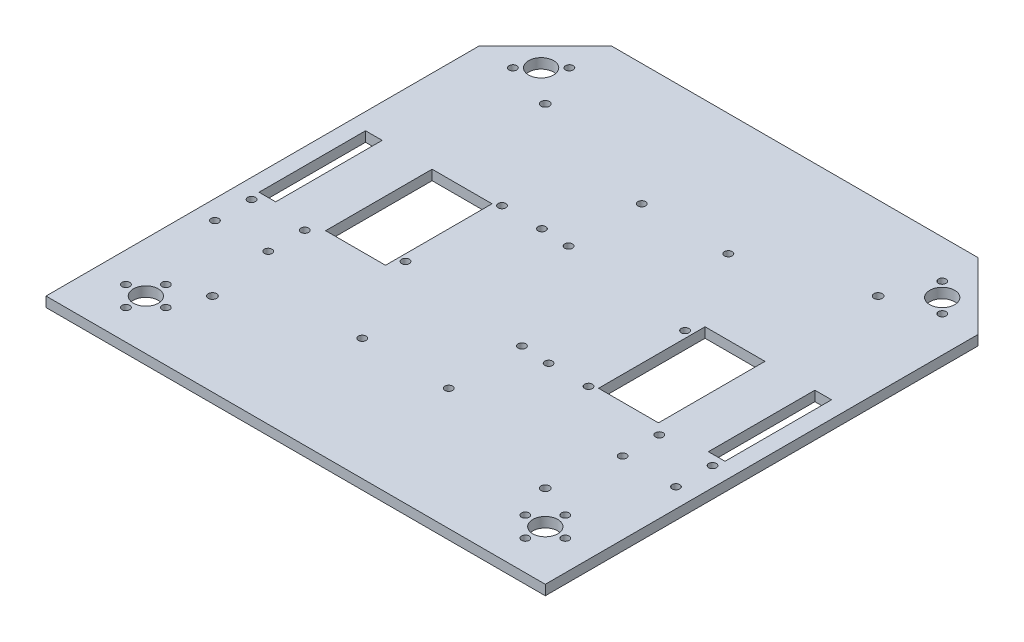
SolidWorks part; units mm, degrees
ref_plane "Plan de face" through (0, 0, 0) normal (0, 0, 1) x (1, 0, 0)
ref_plane "Plan de dessus" through (0, 0, 0) normal (0, 1, 0) x (1, 0, 0)
ref_plane "Plan de droite" through (0, 0, 0) normal (1, 0, 0) x (0, 0, -1)
sketch "Esquisse1" plane through (0, 0, 0) normal (0, 1, 0) x (1, 0, 0)
  line L0 (-150, 0) -> (-150, 260)
  line L2 (150, 0) -> (150, 260)
  line L3 (-150, 260) -> (-110, 260) construction
  line L4 (-110, 260) -> (-110, 300) construction
  line L5 (150, 260) -> (110, 260) construction
  line L6 (110, 260) -> (110, 300) construction
  line L8 (-150, 260) -> (-110, 300)
  line L9 (-110, 300) -> (110, 300)
  line L10 (0, 0) -> (0, 300) construction
  line L11 (110, 300) -> (150, 260)
  line L12 (-150, 0) -> (-120, 0) construction
  line L13 (-120, 18) -> (-120, 0) construction
  line L14 (150, 0) -> (120, 0) construction
  line L15 (120, 18) -> (120, 0) construction
  line L17 (-150, 260) -> (-120, 260) construction
  line L18 (-120, 260) -> (-120, 267.5) construction
  line L19 (150, 260) -> (120, 260) construction
  line L20 (120, 260) -> (120, 268.5) construction
  line L21 (-120, 267.5) -> (-111.5147, 275.9853) construction
  line L22 (-120, 267.5) -> (-128.4853, 259.0147) construction
  line L23 (120, 268.5) -> (128.4853, 260.0147) construction
  line L24 (120, 268.5) -> (111.5147, 276.9853) construction
  line L25 (-150, 0) -> (150, 0) construction
  line L26 (120, 30) -> (120, 18) construction
  line L27 (120, 30) -> (120, 42) construction
  line L28 (-150, 0) -> (150, 0)
  line L29 (-120, 18) -> (-120, 30) construction
  line L30 (-120, 30) -> (-120, 42) construction
  line L32 (150, 150) -> (-150, 150) construction
  line L33 (-120, 30) -> (-108, 30) construction
  line L34 (-120, 30) -> (-132, 30) construction
  line L35 (120, 30) -> (132, 30) construction
  line L36 (120, 30) -> (108, 30) construction
  circle A2 centre (-120, 30) radius 7.5
  circle A4 centre (-120, 267.5) radius 7.5
  circle A5 centre (120, 268.5) radius 7.5
  circle A6 centre (-111.5147, 275.9853) radius 2.3
  circle A7 centre (-128.4853, 259.0147) radius 2.3
  circle A8 centre (111.5147, 276.9853) radius 2.3
  circle A9 centre (128.4853, 260.0147) radius 2.3
  circle A10 centre (120, 30) radius 7.5
  circle A11 centre (120, 42) radius 2.3
  circle A13 centre (-120, 42) radius 2.3
  circle A14 centre (-120, 18) radius 2.3
  circle A16 centre (-132, 30) radius 2.3
  circle A17 centre (-108, 30) radius 2.3
  circle A18 centre (108, 30) radius 2.3
  circle A19 centre (132, 30) radius 2.3
  circle A20 centre (120, 18) radius 2.3
extrude "Boss.-Extru.1" add sketch "Esquisse1" along normal blind 6
sketch "Esquisse7" plane through (0, 6, 0) normal (0, 1, 0) x (1, 0, 0)
  line L0 (0, 150) -> (-130, 150) construction
  line L1 (0, 0) -> (0, 300) construction
  line L2 (150, 150) -> (-150, 150) construction
  line L3 (-130, 150) -> (-130, 182)
  line L4 (-130, 182) -> (-140, 182)
  line L5 (-140, 182) -> (-140, 118)
  line L6 (-140, 118) -> (-130, 118)
  line L7 (-130, 118) -> (-130, 150)
extrude "Enlèv. mat.-Extru.9" cut sketch "Esquisse7" against normal blind 10.5
sketch "Esquisse6" plane through (0, 6, 0) normal (0, 1, 0) x (1, 0, 0)
  line L0 (-142.5, 116) -> (-134.5, 116) construction
  line L2 (-142.5, 116) -> (-142.5, 150) construction
  line L3 (-142.5, 116) -> (-142.5, 108) construction
  line L11 (-142.5, 108) -> (-134.5, 108) construction
  line L12 (-134.5, 108) -> (-134.5, 116) construction
  line L14 (-142.5, 150) -> (-150, 150) construction
  line L15 (-142.5, 116) -> (-102.5, 116) construction
  line L16 (-102.5, 116) -> (-102.5, 108) construction
  line L17 (-102.5, 108) -> (-110.5, 108) construction
  line L18 (-110.5, 108) -> (-110.5, 116) construction
  line L19 (-110.5, 116) -> (-134.5, 116) construction
  line L20 (-134.5, 116) -> (-134.5, 86) construction
  line L21 (-134.5, 86) -> (-142.5, 86) construction
  line L22 (-142.5, 86) -> (-142.5, 94) construction
  line L23 (-142.5, 94) -> (-134.5, 94) construction
  line L24 (-134.5, 94) -> (-134.5, 86) construction
  line L25 (-134.5, 86) -> (-110.5, 86) construction
  line L26 (-110.5, 86) -> (-110.5, 94) construction
  line L27 (-110.5, 94) -> (-102.5, 94) construction
  line L28 (-102.5, 94) -> (-102.5, 86) construction
  line L29 (-102.5, 86) -> (-110.5, 86) construction
  line L30 (-102.5, 94) -> (-110.5, 86) construction
  line L31 (-110.5, 94) -> (-102.5, 86) construction
  line L32 (-142.5, 94) -> (-134.5, 86) construction
  line L33 (-142.5, 86) -> (-134.5, 94) construction
  line L34 (-142.5, 116) -> (-134.5, 108) construction
  line L35 (-142.5, 108) -> (-134.5, 116) construction
  line L71 (-110.5, 116) -> (-102.5, 108) construction
  line L72 (-110.5, 108) -> (-102.5, 116) construction
  line L73 (-110.5, 116) -> (-110.5, 86) construction
  circle A20 centre (-138.5, 90) radius 2.3
  circle A21 centre (-138.5, 112) radius 2.3
  circle A22 centre (-106.5, 112) radius 2.3
  circle A23 centre (-106.5, 90) radius 2.3
  dimension "D1" = 7.5
  dimension "D2" = 34
sketch "Esquisse4" plane through (0, 6, 0) normal (0, 1, 0) x (1, 0, 0)
  line L0 (-150, 150) -> (-100, 150) construction
  line L8 (150, 150) -> (-150, 150) construction
  line L14 (-100, 150) -> (-100, 182)
  line L15 (-100, 250) -> (-100, 50) construction
  line L16 (-100, 150) -> (-100, 118)
  line L17 (-100, 118) -> (-64, 118)
  line L18 (-64, 118) -> (-64, 182)
  line L19 (-64, 182) -> (-100, 182)
sketch "Esquisse9" plane through (0, 6, 0) normal (0, 1, 0) x (1, 0, 0)
  line L0 (-150, 0) -> (150, 0) construction
  line L1 (150, 0) -> (150, 300) construction
  line L2 (150, 300) -> (-150, 300) construction
  line L3 (-150, 300) -> (-150, 0) construction
  line L5 (-150, 0) -> (-150, 300) construction
  line L6 (150, 0) -> (0, 0) construction
  line L7 (0, 0) -> (0, 50) construction
  line L8 (0, 0) -> (0, 300) construction
  line L9 (0, 50) -> (100, 50) construction
  line L10 (100, 50) -> (100, 250) construction
  line L11 (100, 250) -> (-100, 250) construction
  line L12 (-100, 250) -> (-100, 50) construction
  line L13 (-100, 50) -> (0, 50) construction
  line L18 (100, 250) -> (94.3431, 244.3431) construction
  line L21 (-150, 0) -> (150, 300) construction
  circle A0 centre (-100, 50) radius 2.5
  circle A1 centre (100, 50) radius 2.5
  circle A2 centre (100, 250) radius 2.5
  circle A3 centre (-100, 250) radius 2.5
extrude "Enlèv. mat.-Extru.10" cut sketch "Esquisse6" against normal blind 50
extrude "Enlèv. mat.-Extru.11" cut sketch "Esquisse4" against normal blind 50
sketch "Esquisse3" plane through (0, 6, 0) normal (0, 1, 0) x (1, 0, 0)
  line L55 (150, 150) -> (65, 150) construction
  line L56 (150, 150) -> (-150, 150) construction
mirror "Symétrie1" about plane through (0, 0, 0) normal (1, 0, 0) of "Enlèv. mat.-Extru.9"
mirror "Symétrie2" about plane through (0, 0, 0) normal (1, 0, 0) of "Enlèv. mat.-Extru.11"
mirror "Symétrie3" about plane through (0, 0, 0) normal (1, 0, 0) of "Enlèv. mat.-Extru.10"
extrude "Enlèv. mat.-Extru.12" cut sketch "Esquisse9" against normal blind 35
sketch "Esquisse11" plane through (0, 6, 0) normal (0, 1, 0) x (1, 0, 0)
  line L0 (-64, 150) -> (-64, 130) construction
  line L2 (-64, 118) -> (-64, 182) construction
  line L3 (32, 223) -> (-23, 223) construction
  line L4 (-23, 223) -> (-23, 187) construction
  line L5 (-23, 187) -> (-15, 187) construction
  line L6 (-15, 187) -> (-15, 179) construction
  line L7 (-64, 150) -> (-64, 180) construction
  line L8 (-64, 180) -> (-32, 180) construction
  line L9 (-32, 180) -> (-32, 77) construction
  line L10 (-64, 130) -> (-56, 130) construction
  line L11 (-56, 130) -> (-56, 122) construction
  line L12 (-56, 122) -> (-64, 130) construction
  line L13 (-64, 130) -> (-56, 130) construction
  line L14 (-56, 130) -> (-64, 122) construction
  line L15 (-64, 122) -> (-56, 122) construction
  line L16 (-64, 180) -> (-64, 188) construction
  line L17 (-64, 188) -> (-56, 188) construction
  line L18 (-56, 188) -> (-56, 180) construction
  line L19 (-56, 180) -> (-64, 188) construction
  line L20 (-64, 188) -> (-56, 188) construction
  line L21 (64, 150) -> (64, 170) construction
  line L22 (64, 170) -> (56, 170) construction
  line L23 (56, 170) -> (56, 178) construction
  line L24 (56, 178) -> (64, 178) construction
  line L25 (64, 178) -> (64, 170) construction
  line L26 (64, 170) -> (56, 178) construction
  line L27 (56, 178) -> (56, 170) construction
  line L28 (56, 170) -> (64, 178) construction
  line L29 (64, 150) -> (64, 120) construction
  line L30 (64, 118) -> (64, 182) construction
  line L31 (64, 120) -> (32, 120) construction
  line L32 (32, 120) -> (32, 165) construction
  line L33 (32, 165) -> (37, 165) construction
  line L34 (37, 165) -> (37, 129.3158) construction
  line L35 (37, 129.3158) -> (64, 129.3158) construction
  line L36 (32, 120) -> (32, 223) construction
  line L37 (-15, 179) -> (-23, 179) construction
  line L38 (-23, 179) -> (-23, 187) construction
  line L39 (-23, 187) -> (-15, 179) construction
  line L40 (-15, 179) -> (-15, 187) construction
  line L41 (-15, 187) -> (-23, 179) construction
  line L42 (32, 223) -> (37, 223) construction
  line L43 (37, 223) -> (37, 231) construction
  line L44 (37, 231) -> (29, 231) construction
  line L45 (-23, 223) -> (-23, 231) construction
  line L46 (-23, 231) -> (-15, 231) construction
  line L47 (64, 120) -> (64, 112) construction
  line L48 (64, 112) -> (56, 112) construction
  line L49 (56, 112) -> (56, 120) construction
  line L50 (56, 120) -> (64, 112) construction
  line L51 (64, 112) -> (64, 120) construction
  line L52 (64, 120) -> (56, 112) construction
  line L53 (56, 112) -> (56, 120) construction
  line L54 (56, 120) -> (32, 120) construction
  line L55 (32, 120) -> (32, 112) construction
  line L56 (32, 112) -> (40, 112) construction
  line L57 (40, 112) -> (40, 120) construction
  line L58 (40, 120) -> (32, 112) construction
  line L59 (32, 112) -> (32, 120) construction
  line L60 (32, 120) -> (40, 112) construction
  line L61 (-15, 231) -> (-15, 223) construction
  line L62 (-15, 223) -> (-23, 231) construction
  line L63 (-23, 231) -> (-23, 223) construction
  line L64 (-23, 223) -> (-15, 231) construction
  line L65 (29, 231) -> (29, 223) construction
  line L66 (29, 223) -> (37, 231) construction
  line L67 (37, 231) -> (29, 231) construction
  line L68 (29, 231) -> (37, 223) construction
  line L69 (-56, 188) -> (-64, 180) construction
  line L70 (-64, 180) -> (-32, 180) construction
  line L71 (-32, 180) -> (-32, 188) construction
  line L72 (-32, 188) -> (-40, 188) construction
  line L73 (-40, 188) -> (-40, 180) construction
  line L74 (-40, 180) -> (-32, 188) construction
  line L75 (-32, 188) -> (-40, 188) construction
  line L76 (-40, 188) -> (-32, 180) construction
  line L77 (-32, 180) -> (-32, 77) construction
  line L78 (-32, 77) -> (-37, 77) construction
  line L79 (-37, 77) -> (-37, 69) construction
  line L80 (-37, 69) -> (-29, 69) construction
  line L81 (-29, 69) -> (-29, 77) construction
  line L82 (-29, 77) -> (-37, 69) construction
  line L83 (-37, 69) -> (-37, 77) construction
  line L84 (-37, 77) -> (-29, 69) construction
  line L85 (-29, 69) -> (-29, 77) construction
  line L86 (-29, 77) -> (-37, 77) construction
  line L87 (-37, 77) -> (23, 77) construction
  line L88 (23, 77) -> (23, 69) construction
  line L89 (23, 69) -> (15, 69) construction
  line L90 (15, 69) -> (15, 77) construction
  line L91 (15, 77) -> (23, 69) construction
  line L92 (23, 69) -> (23, 77) construction
  line L93 (23, 77) -> (15, 69) construction
  line L94 (15, 69) -> (23, 69) construction
  line L95 (23, 69) -> (23, 77) construction
  line L96 (23, 77) -> (23, 113) construction
  line L97 (23, 113) -> (-32, 113) construction
  line L98 (23, 113) -> (23, 121) construction
  line L99 (23, 121) -> (15, 121) construction
  line L100 (15, 121) -> (15, 113) construction
  line L101 (15, 113) -> (23, 121) construction
  line L102 (23, 121) -> (15, 121) construction
  line L103 (15, 121) -> (23, 113) construction
  circle A4 centre (36, 116) radius 2.3
  circle A5 centre (60, 116) radius 2.3
  circle A7 centre (60, 174) radius 2.3
  circle A8 centre (-19, 227) radius 2.3
  circle A12 centre (-19, 183) radius 2.3
  circle A13 centre (33, 227) radius 2.3
  circle A14 centre (19, 117) radius 2.3
  circle A15 centre (19, 73) radius 2.3
  circle A17 centre (-33, 73) radius 2.3
  circle A18 centre (-60, 126) radius 2.3
  circle A19 centre (-36, 184) radius 2.3
  circle A20 centre (-60, 184) radius 2.3
  dimension "D1" = 50
  dimension "D2" = 32
  dimension "D3" = 20
extrude "Enlèv. mat.-Extru.15" cut sketch "Esquisse11" against normal blind 10
